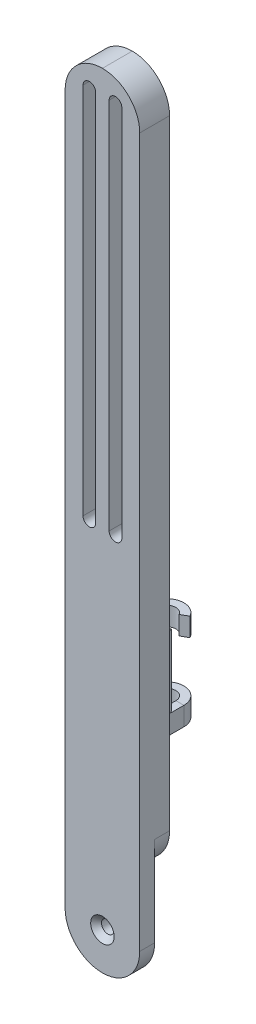
SolidWorks part; units mm, degrees
note: '?' marks a value the reader was unsure of.
ref_plane "Front Plane" through (0, 0, 0) normal (1, 0, 0) x (0, 1, 0)
ref_plane "Top Plane" through (0, 0, 0) normal (0, 0, 1) x (0, 1, 0)
ref_plane "Right Plane" through (0, 0, 0) normal (0, 1, 0) x (-1, 0, 0)
sketch "Sketch1" plane through (0, 0, 0) normal (0, 0, 1) x (0, 1, 0)
  line L0 (-6.5, 3.5) -> (-100, 3.5) construction
  line L1 (100, -10) -> (-100, -10)
  line L2 (100, -10) -> (100, 10)
  line L3 (100, 10) -> (-100, 10)
  line L4 (-100, -10) -> (-100, 10)
  line L5 (100, -10) -> (-100, 10) construction
  line L6 (100, 10) -> (-100, -10) construction
  line L7 (-6.5, 3.5) -> (93.5, 3.5) construction
  line L8 (-6.5, 3.5) -> (93.5, 3.5) construction
  line L9 (93.5, 3.5) -> (100, 3.5) construction
  line L10 (-6.5, -3.5) -> (-100, -3.5) construction
  line L11 (-6.5, 5.2) -> (93.5, 5.2)
  line L12 (-6.5, 1.8) -> (93.5, 1.8)
  line L13 (-6.5, -3.5) -> (93.5, -3.5) construction
  line L14 (-6.5, -3.5) -> (93.5, -3.5) construction
  line L15 (93.5, -3.5) -> (100, -3.5) construction
  line L16 (-6.5, -1.8) -> (93.5, -1.8)
  line L17 (-6.5, -5.2) -> (93.5, -5.2)
  line L18 (43.5, -3.5) -> (43.5, 3.5) construction
  line L19 (43.5, 3.5) -> (43.5, 10) construction
  line L20 (43.5, -3.5) -> (43.5, -10) construction
  arc A0 (-6.5, 5.2) -> (-6.5, 1.8) centre (-6.5, 3.5) ccw
  arc A1 (93.5, 1.8) -> (93.5, 5.2) centre (93.5, 3.5) ccw
  arc A3 (-6.5, -1.8) -> (-6.5, -5.2) centre (-6.5, -3.5) ccw
  arc A4 (93.5, -5.2) -> (93.5, -1.8) centre (93.5, -3.5) ccw
  arc A5 (-100, -10) -> (-100, 10) centre (-100, 0) cw
  point P0 (0, 0)
  point P6 (43.5, 3.5)
  point P18 (43.5, -3.5)
  point P38 (-110, 0)
  dimension "D4" = 1.7
  dimension "D1" = 200
  dimension "D2" = 20
  dimension "D3" = 7
  dimension "D5" = 100
  dimension "D6" = 6.5
extrude "Boss-Extrude1" add sketch "Sketch1" along normal blind 8
fillet "Fillet1" radius 10 2 edges at (-10, 100, 4) (10, 100, 4)
sketch "Sketch8" plane through (0, 0, 0) normal (0, 0, -1) x (1, 0, 0)
  line L0 (-10, 100) -> (10, 100) construction
  line L1 (0, 110) -> (0, 86) construction
  line L3 (-10, 86) -> (10, 86) construction
  line L4 (-10, -90) -> (-10, 100) construction
  line L6 (0, 86) -> (0, 76) construction
  line L16 (10, -90) -> (10, 100) construction
  line L18 (-10, 76) -> (10, 76)
  line L19 (-10, 76) -> (-10, 110)
  line L20 (-10, 110) -> (10, 110)
  line L21 (10, 76) -> (10, 110)
  arc A3 (10, 100) -> (-10, 100) centre (0, 100) ccw construction
  arc A4 (-10, 76) -> (10, 76) centre (0, 76) cw
  point P8 (0, 86)
  dimension "D1" = 24
extrude "Cut-Extrude8" cut sketch "Sketch8" against normal blind 4 contours L19 A4 L21 L20
sketch "Sketch12" plane through (0, 0, 8) normal (0, 0, 1) x (1, 0, 0)
  line L0 (-10, -100) -> (10, -100) construction
  point P6 (0, -100)
hole_wizard "CSK for M3 Countersunk Flat Head Screw2" positions "Sketch12" profile "Sketch13" countersink size "M3" standard "ISO"
sketch "Sketch13" plane through (0, -100, 8) normal (1, 0, 0) x (0, -1, 0)
  line L0 (0, 0) -> (0, 9.5215)
  line L1 (0, 9.5215) -> (1.7, 8.5)
  line L2 (1.7, 8.5) -> (1.7, 1.45)
  line L3 (1.7, 1.45) -> (3.15, 0)
  line L5 (3.15, 0) -> (0, 0)
  line L6 (-1.7, 1.45) -> (-3.15, 0) construction
  line L10 (0, 9.5215) -> (-1.7, 8.5) construction
  line L11 (0, -6.35) -> (0, 107.95) construction
  dimension "Hole Dia." = 3.4
  dimension "Hole Depth" = 8.5
  dimension "Near C'Sink Dia." = 6.3
  dimension "Near C'Sink Angle" = 90
  dimension "Drill Angle" = 118
sketch "Sketch14" plane through (0, 0, 0) normal (0, 0, 1) x (1, 0, 0)
  line L0 (-2.65, -12.85) -> (-7.35, -32.85) construction
  line L1 (-7.35, -12.85) -> (-2.65, -12.85)
  line L2 (-7.35, -12.85) -> (-7.35, -32.85)
  line L3 (-7.35, -32.85) -> (-2.65, -32.85)
  line L4 (-2.65, -12.85) -> (-2.65, -32.85)
  line L13 (-7.35, -12.85) -> (-2.65, -32.85) construction
  line L14 (-10, -22.85) -> (-7.35, -22.85) construction
  line L15 (-5, -12.85) -> (-5, -10.7) construction
  line L16 (-7.35, -12.85) -> (-9.5, -12.85) construction
  line L17 (0, -8.6713) -> (0, -37.0287) construction
  line L18 (-10, 90) -> (-10, -100) construction
  line L19 (-2.65, -22.85) -> (0, -22.85) construction
  line L20 (-10, -22.85) -> (10, -22.85) construction
  line L21 (10, 90) -> (10, -100) construction
  line L22 (-2.65, -12.85) -> (-0.5, -12.85) construction
  line L31 (-9.5, -10.7) -> (-0.5, -10.7)
  line L32 (-9.5, -10.7) -> (-9.5, -35)
  line L33 (-9.5, -35) -> (-0.5, -35)
  line L34 (-0.5, -10.7) -> (-0.5, -35)
  line L35 (-5, -32.85) -> (-5, -35) construction
  point P9 (-5, -22.85)
  point P23 (0, -22.85)
  point P24 (0, -22.85)
  point P25 (0, 0)
  point P30 (-5, -35)
  dimension "D1" = 9
  dimension "D2" = 20
  dimension "D4" = 4.7
  dimension "D5" = 65
extrude "Boss-Extrude2" add sketch "Sketch14" against normal blind 2
fillet "Fillet3" radius 1.65 4 edges at (-9.5, -22.85, -2) (-5, -35, -2) (-0.5, -22.85, -2) (-5, -10.7, -2)
sketch "Sketch16" plane through (0, 0, -2) normal (0, 0, 1) x (1, 0, 0)
  line L0 (-0.5, -10.7) -> (-0.5, -35) construction
  line L6 (-9.5, -10.7) -> (-9.5, -35) construction
  line L7 (-9.5, -10.7) -> (-0.5, -10.7) construction
  line L8 (-0.5, -10.7) -> (-0.5, -35)
  line L9 (-9.5, -35) -> (-0.5, -35)
  line L10 (-9.5, -10.7) -> (-9.5, -35)
  line L11 (-9.5, -10.7) -> (-0.5, -10.7)
  line L12 (-9.5, -22.85) -> (-7.35, -22.85) construction
  line L13 (-7.35, -10.7) -> (-2.65, -10.7)
  line L14 (-7.35, -10.7) -> (-7.35, -35)
  line L15 (-7.35, -35) -> (-2.65, -35)
  line L16 (-2.65, -10.7) -> (-2.65, -35)
  line L17 (-2.65, -22.85) -> (-0.5, -22.85) construction
  line L18 (-7.35, -22.85) -> (-2.65, -22.85) construction
  line L19 (-2.65, -30) -> (-0.5, -30)
  line L20 (-2.65, -30) -> (-2.65, -35)
  line L21 (-2.65, -35) -> (-0.5, -35)
  line L22 (-0.5, -30) -> (-0.5, -35)
  point P14 (-5, -22.85)
  dimension "D1" = 4.7
  dimension "D2" = 5
ref_plane "Plane1" through (0, -33.35, 0) normal (0, -1, 0) x (-1, 0, 0)
ref_axis "Axis1" through (-5, -22.85, -4.2148) along (0, 0, -1)?
sketch "Sketch17" plane through (0, -33.35, 0) normal (0, -1, 0) x (-1, 0, 0)
  line L0 (2.65, 2) -> (2.65, 4.35)
  line L1 (2.65, 4.35) -> (5, 4.35)
  line L3 (2.15, 2) -> (7.85, 2) construction
  arc A0 (2.65, 4.35) -> (7.0494, 5.5) centre (5, 4.35) cw
  point P3 (4.3975, 4.35)
  point P8 (2.7523, 2.0367)
  point P9 (0, 0)
  point P10 (7.3389, 5.5)
  point P11 (0, 0)
  point P13 (0, 0)
  dimension "D1" = 2.35
  dimension "D2" = 3.5
  dimension "D3" = 2.35
extrude "Boss-Extrude3" add sketch "Sketch16" along normal up to surface (2 mm away) up to face at (0, 24.4284, 0)
sketch "Sketch18" plane through (0, 0, -2) normal (0, 0, 1) x (1, 0, 0)
  line L0 (-2.65, -30) -> (-0.5, -30) construction
  line L1 (-2.65, -30) -> (-0.5, -30)
  line L3 (-0.5, -30) -> (-2.65, -30)
  line L4 (-0.5, -30) -> (-0.5, -35)
  line L5 (-0.5, -35) -> (-2.65, -35)
  line L6 (-2.65, -30) -> (-2.65, -35)
sweep "Sweep3" add profiles "Sketch18" path "Sketch17"
pattern_circular "CirPattern1" count 2 every 180 about axis through (-5, -22.85, 0) along (0, 0, 1) of "Boss-Extrude3", "Sweep3"
sketch "Sketch22" plane through (0, 0, 0) normal (0, 0, -1) x (1, 0, 0)
  line L0 (-10, 32.5) -> (10, 32.5) construction
  line L1 (-0.5, 35) -> (0, 35) construction
  line L2 (-0.5, 35) -> (-0.5, 32.5) construction
  line L3 (-0.5, 32.5) -> (0, 32.5) construction
  line L4 (0, 35) -> (0, 32.5) construction
  line L5 (-10, -90) -> (-10, 76) construction
  line L6 (10, -90) -> (10, 76) construction
  point P11 (0, 0)
  point P12 (0, 32.5)
  point P13 (0, 0)
  point P14 (0, 0)
  dimension "D1" = 2.5
ref_axis "Axis2" through (0, -32.5, 0) along (0, 0, -1)?
pattern_circular "CirPattern2" count 2 every 180 about axis through (0, -32.5, 0) along (0, 0, 1) of "Boss-Extrude2", "Fillet3", "Boss-Extrude3", "Sweep3", "CirPattern1"
